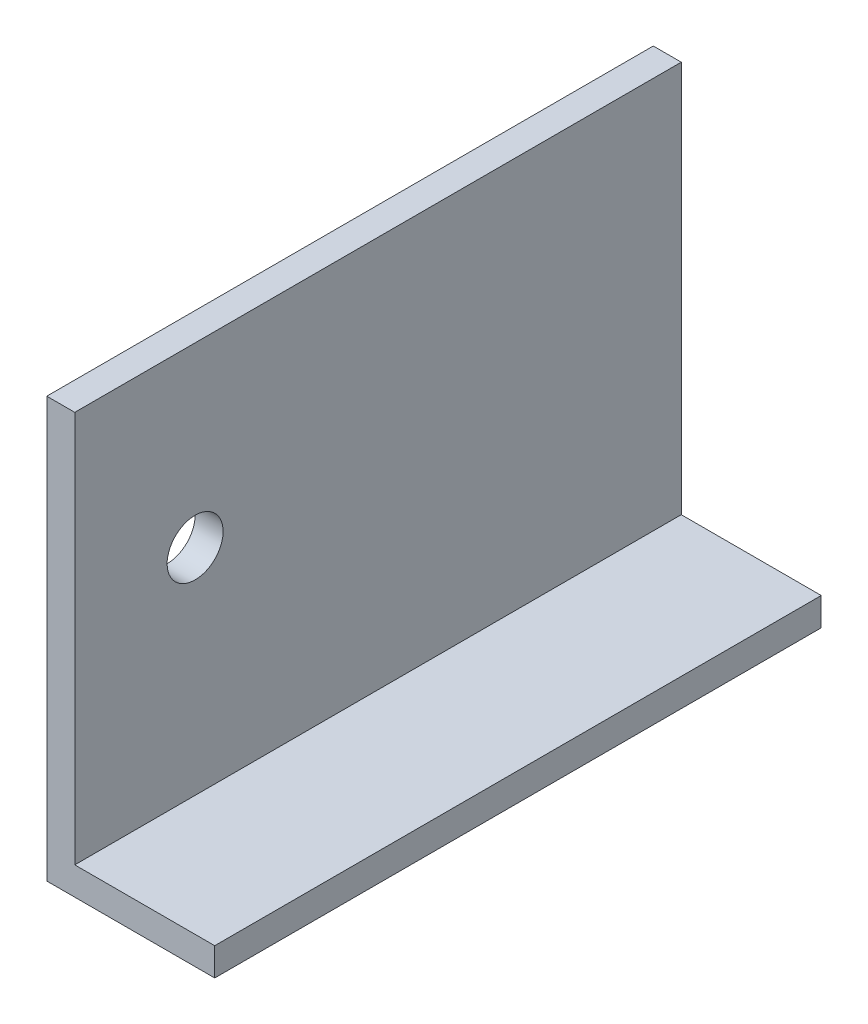
SolidWorks part; units mm, degrees
ref_plane "前视基准面" through (0, 0, 0) normal (0, 0, 1) x (1, 0, 0)
ref_plane "上视基准面" through (0, 0, 0) normal (0, 1, 0) x (1, 0, 0)
ref_plane "右视基准面" through (0, 0, 0) normal (1, 0, 0) x (0, 0, -1)
other "Configuration Table"
sketch "草图1" plane through (0, 0, 0) normal (0, 0, 1) x (1, 0, 0)
  line L1 (0, 45) -> (3, 45)
  line L2 (0, 45) -> (0, 0)
  line L3 (0, 0) -> (3, 0)
  line L4 (3, 45) -> (3, 0)
  line L5 (3, 3) -> (18, 3)
  line L6 (3, 3) -> (3, 0)
  line L7 (3, 0) -> (18, 0)
  line L8 (18, 3) -> (18, 0)
  dimension "D1" = 3
  dimension "D2" = 45
  dimension "D3" = 15
  dimension "D4" = 3
extrude "凸台-拉伸1" add sketch "草图1" along normal blind 65 contours L4 L1 L2 L3 | L6 L5 L8 L7
sketch "草图2" plane through (3, 0, 0) normal (1, 0, 0) x (0, 0, -1)
  line L0 (-65, 45) -> (-65, 3) construction
  line L2 (-65, 45) -> (0, 45) construction
  circle A0 centre (-52.1, 26) radius 3
  dimension "D1" = 6
  dimension "D2" = 12.9
  dimension "D3" = 19
extrude "切除-拉伸1" cut sketch "草图2" against normal blind 64.5
